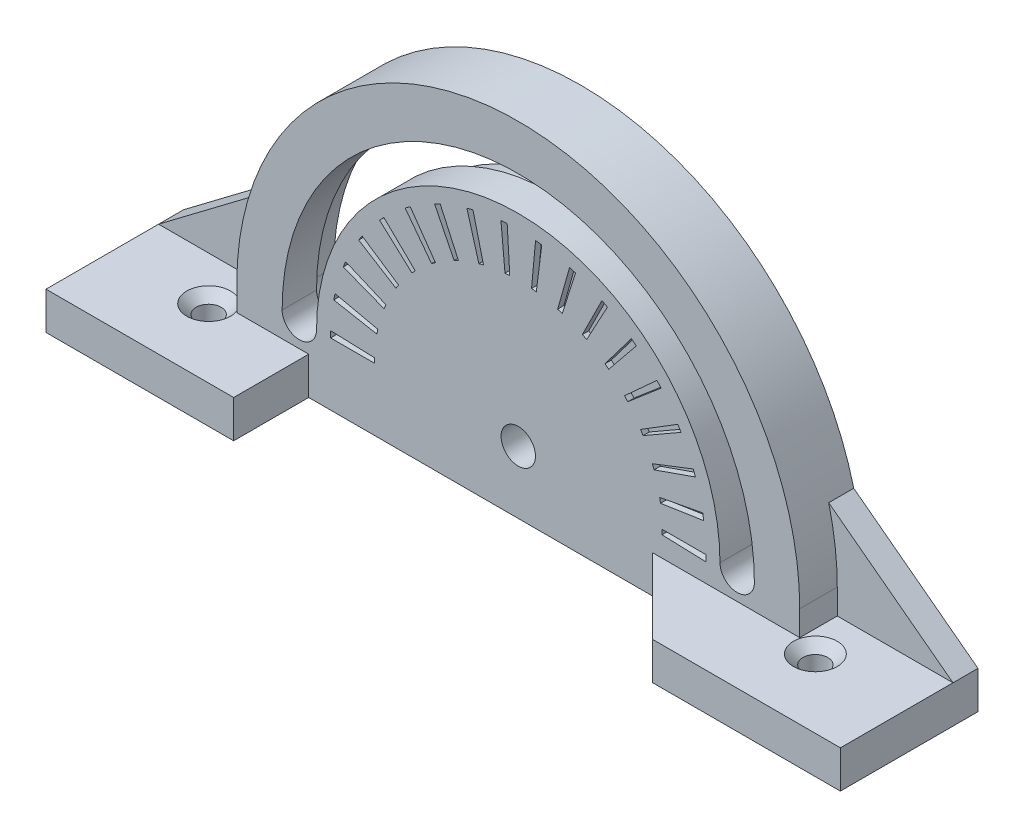
SolidWorks part; units mm, degrees
ref_plane "Top Plane" through (0, 0, 0) normal (0, 0, 1) x (1, 0, 0)
ref_plane "Right Plane" through (0, 0, 0) normal (0, 1, 0) x (1, 0, 0)
ref_plane "Front Plane" through (0, 0, 0) normal (1, 0, 0) x (0, 0, -1)
sketch "Sketch1" plane through (0, 0, 0) normal (0, 0, 1) x (1, 0, 0)
  line L0 (-45, 0) -> (45, 0) construction
  line L1 (-45, 0) -> (-45, -10)
  line L2 (-45, -10) -> (45, -10)
  line L3 (45, -10) -> (45, 0)
  arc A0 (-45, 0) -> (45, 0) centre (0, 0) cw
  circle A1 centre (0, 0) radius 2.75
  arc A2 (-32.25, 0) -> (32.25, 0) centre (0, 0) cw
  arc A3 (-37.75, 0) -> (37.75, 0) centre (0, 0) cw
  arc A4 (-37.75, 0) -> (-32.25, 0) centre (-35, 0) ccw
  arc A5 (32.25, 0) -> (37.75, 0) centre (35, 0) ccw
  point P5 (0, 0)
  dimension "D3" = 5.5
  dimension "D5" = 5.5
  dimension "D1" = 90
  dimension "D2" = 10
  dimension "D4" = 10
extrude "Boss-Extrude1" add sketch "Sketch1" along normal blind 10
sketch "Sketch2" plane through (0, 0, 0) normal (0, 0, -1) x (-1, 0, 0)
  line L0 (4.9075, 0) -> (2.4537, -4.25)
  line L1 (2.4537, -4.25) -> (-2.4537, -4.25)
  line L2 (-2.4537, -4.25) -> (-4.9075, 0)
  line L3 (-4.9075, 0) -> (-2.4537, 4.25)
  line L4 (-2.4537, 4.25) -> (2.4537, 4.25)
  line L5 (2.4537, 4.25) -> (4.9075, 0)
  circle A0 centre (0, 0) radius 4.9075 construction
  arc A1 (-30.5, 0) -> (30.5, 0) centre (0, 0) cw
  arc A2 (-39.5, 0) -> (39.5, 0) centre (0, 0) cw
  arc A3 (39.5, 0) -> (30.5, 0) centre (35, 0) cw
  circle A5 centre (35, 0) radius 4.5 construction
  circle A6 centre (-35, 0) radius 4.5 construction
  arc A7 (-30.5, 0) -> (-39.5, 0) centre (-35, 0) cw
  dimension "D1" = 8.5
  dimension "D2" = 9
extrude "Cut-Extrude1" cut sketch "Sketch2" against normal blind 4.5
sketch "Sketch3" plane through (0, 0, 10) normal (0, 0, 1) x (1, 0, 0)
  line L0 (-29.9833, 0.9999) -> (0, 0) construction
  line L1 (0, 0) -> (-30, 0) construction
  line L2 (-29.9833, 0.9999) -> (-22.9872, 0.7666)
  line L3 (-30, 0) -> (-23, 0)
  arc A0 (-29.9833, 0.9999) -> (-30, 0) centre (0, 0) ccw
  arc A1 (45, 0) -> (-45, 0) centre (0, 0) ccw construction
  arc A2 (-22.9872, 0.7666) -> (-23, 0) centre (0, 0) ccw
  dimension "D1" = 15
  dimension "D2" = 7
  dimension "D3" = 1
extrude "Cut-Extrude2" cut sketch "Sketch3" against normal blind 1
pattern_circular "CirPattern1" count 18 over 180 about axis through (0, 0, 10) along (0, 0, -1) of "Cut-Extrude2"
sketch "Sketch4" plane through (0, -10, 0) normal (0, -1, 0) x (1, 0, 0)
  line L0 (63.5, 22) -> (33.5, 0) construction
  line L1 (63.5, 0) -> (33.5, 0)
  line L2 (63.5, 0) -> (63.5, 22)
  line L3 (63.5, 22) -> (33.5, 22)
  line L4 (33.5, 0) -> (33.5, 22)
  line L8 (45, 10) -> (45, 0) construction
  line L9 (-45, 0) -> (45, 0) construction
  circle A0 centre (48.5, 11) radius 2
  point P6 (0, 0)
  point P9 (33, 24.0907)
  point P10 (0, 0)
  dimension "D1" = 4
  dimension "D4" = 1.5
  dimension "D2" = 22
  dimension "D3" = 30
extrude "Boss-Extrude2" add sketch "Sketch4" against normal blind 6
chamfer "Chamfer3" distance 12 angle 45 1 edges at (33.5, -7, 10)
sketch "Sketch5" plane through (0, 0, 0) normal (0, 0, -1) x (-1, 0, 0)
  line L0 (-63.5, -4) -> (-43.6348, 11)
  line L1 (-43.6348, 11) -> (-43.6348, -4)
  line L2 (-43.6348, -4) -> (-63.5, -4)
  arc A0 (45, 0) -> (-45, 0) centre (0, 0) ccw construction
  dimension "D1" = 15
extrude "Boss-Extrude3" add sketch "Sketch5" against normal blind 4
chamfer "Chamfer4" distance 1.5 angle 45 1 edges at (48.5, -4, 9)
mirror "Mirror1" about plane through (0, 0, 0) normal (1, 0, 0) of "Boss-Extrude3", "Chamfer4", "Boss-Extrude2"
